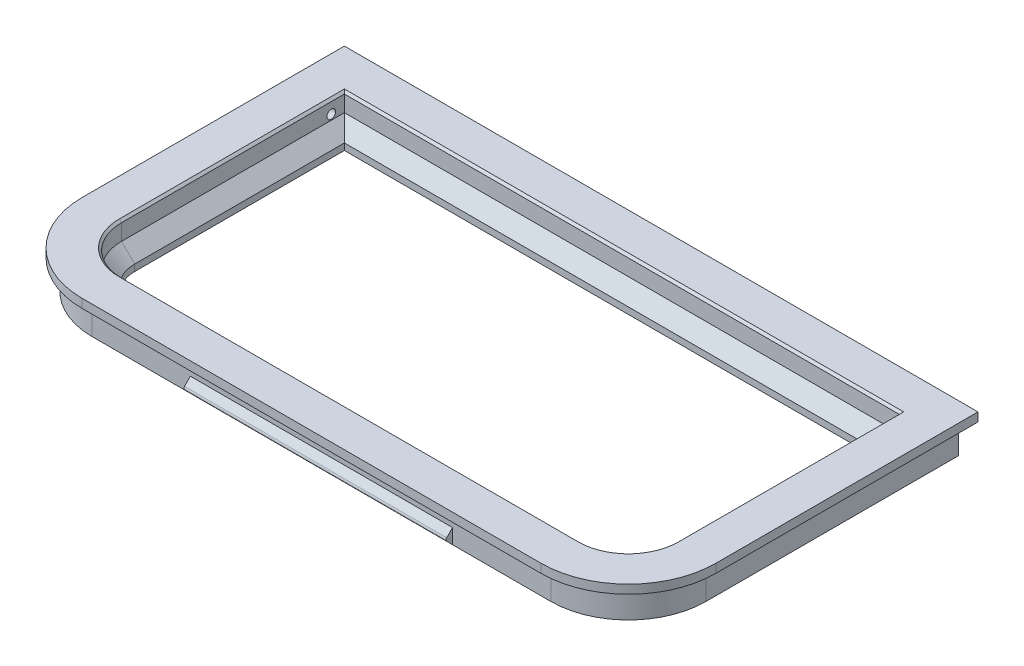
SolidWorks part; units mm, degrees
material "ПК/АБС"
ref_plane "Спереди" through (0, 0, 0) normal (0, 0, 1) x (1, 0, 0)
ref_plane "Сверху" through (0, 0, 0) normal (0, 1, 0) x (1, 0, 0)
ref_plane "Справа" through (0, 0, 0) normal (1, 0, 0) x (0, 0, -1)
sketch "Эскиз1" plane through (0, 0, 0) normal (0, 1, 0) x (1, 0, 0)
  line L1 (-72.5, -40) -> (72.5, -40)
  line L2 (-72.5, -40) -> (-72.5, 40)
  line L3 (-72.5, 40) -> (72.5, 40)
  line L4 (72.5, -40) -> (72.5, 40)
  line L5 (-72.5, -40) -> (72.5, 40) construction
  line L6 (-72.5, 40) -> (72.5, -40) construction
  point P0 (0, 0)
  dimension "D1" = 145
  dimension "D2" = 80
extrude "Бобышка-Вытянуть1" add sketch "Эскиз1" along normal blind 2
fillet "Скругление1" radius 20 2 edges at (-72.5, 1, 40) (72.5, 1, 40)
sketch "Эскиз2" plane through (0, 2, 0) normal (0, 1, 0) x (1, 0, 0)
  line L8 (-63.5, 31) -> (-63.5, -20)
  line L9 (-52.5, -31) -> (52.5, -31)
  line L10 (63.5, -20) -> (63.5, 31)
  line L11 (63.5, 31) -> (-63.5, 31)
  line L12 (-63.5, 31) -> (-63.5, -20)
  line L13 (-52.5, -31) -> (52.5, -31)
  line L14 (63.5, -20) -> (63.5, 31)
  line L15 (63.5, 31) -> (-63.5, 31)
  arc A4 (-63.5, -20) -> (-52.5, -31) centre (-52.5, -20) ccw
  arc A5 (52.5, -31) -> (63.5, -20) centre (52.5, -20) ccw
  arc A6 (-63.5, -20) -> (-52.5, -31) centre (-52.5, -20) ccw
  arc A7 (52.5, -31) -> (63.5, -20) centre (52.5, -20) ccw
  dimension "D1" = 9
extrude "Вырез-Вытянуть1" cut sketch "Эскиз2" against normal blind 2
sketch "Эскиз3" plane through (0, 0, 0) normal (0, -1, 0) x (1, 0, 0)
  line L15 (-63.5, -31) -> (-63.5, 20) construction
  line L16 (63.5, -31) -> (-63.5, -31) construction
  line L17 (63.5, 20) -> (63.5, -31) construction
  line L18 (-52.5, 31) -> (52.5, 31) construction
  line L19 (70.25, -37.75) -> (70.25, 20)
  line L20 (-70.25, -37.75) -> (70.25, -37.75)
  line L21 (-70.25, 20) -> (-70.25, -37.75)
  line L22 (52.5, 37.75) -> (-52.5, 37.75)
  line L23 (70.25, -37.75) -> (70.25, 20)
  line L24 (-70.25, -37.75) -> (70.25, -37.75)
  line L25 (-70.25, 20) -> (-70.25, -37.75)
  line L26 (52.5, 37.75) -> (-52.5, 37.75)
  line L27 (-63.5, -31) -> (-63.5, 20)
  line L28 (63.5, -31) -> (-63.5, -31)
  line L29 (63.5, 20) -> (63.5, -31)
  line L30 (-52.5, 31) -> (52.5, 31)
  arc A6 (-52.5, 31) -> (-63.5, 20) centre (-52.5, 20) ccw construction
  arc A7 (63.5, 20) -> (52.5, 31) centre (52.5, 20) ccw construction
  arc A8 (70.25, 20) -> (52.5, 37.75) centre (52.5, 20) ccw
  arc A9 (-52.5, 37.75) -> (-70.25, 20) centre (-52.5, 20) ccw
  arc A10 (70.25, 20) -> (52.5, 37.75) centre (52.5, 20) ccw
  arc A11 (-52.5, 37.75) -> (-70.25, 20) centre (-52.5, 20) ccw
  arc A12 (-52.5, 31) -> (-63.5, 20) centre (-52.5, 20) ccw
  arc A13 (63.5, 20) -> (52.5, 31) centre (52.5, 20) ccw
  dimension "D1" = 6.75
extrude "Бобышка-Вытянуть2" add sketch "Эскиз3" along normal blind 2
sketch "Эскиз5" plane through (0, 0, 0) normal (1, 0, 0) x (0, 0, -1)
  line L0 (-20, 0) -> (40, 0) construction
  line L7 (37.75, -2) -> (31, -2)
  line L9 (31, -2) -> (31, -6.7)
  line L10 (31, -6.7) -> (37.75, -6.7)
  line L11 (37.75, -6.7) -> (39.45, -5)
  line L12 (39.45, -5) -> (37.75, -3.3)
  line L13 (37.75, -3.3) -> (37.75, -2)
  line L14 (31, -2) -> (31, 2) construction
  line L15 (31, -2) -> (31, 2) construction
  line L16 (-31, -2) -> (-31, 2) construction
  line L17 (-31, -2) -> (-31, 2) construction
  line L18 (-31, -2) -> (-31, -6.7)
  line L19 (-31, -6.7) -> (-37.75, -6.7)
  line L20 (-37.75, -6.7) -> (-39.45, -5)
  line L21 (-39.45, -5) -> (-37.75, -3.3)
  line L22 (-37.75, -3.3) -> (-37.75, -2)
  line L23 (-37.75, -2) -> (-31, -2)
  dimension "D1" = 5
  dimension "D2" = 1.7
  dimension "D4" = 1.7
extrude "Бобышка-Вытянуть4" add sketch "Эскиз5" along normal mid plane 15
sketch "Эскиз6" plane through (0, 0, 0) normal (1, 0, 0) x (0, 0, -1)
  line L6 (-39.45, -5) -> (-37.75, -6.7)
  line L7 (-37.75, -6.7) -> (-31, -6.7)
  line L8 (-31, -6.7) -> (-31, -2)
  line L9 (-31, -2) -> (-37.75, -2)
  line L10 (-37.75, -2) -> (-37.75, -3.3)
  line L11 (-37.75, -3.3) -> (-39.45, -5)
  line L12 (-39.45, -5) -> (-37.75, -6.7)
  line L13 (-37.75, -6.7) -> (-31, -6.7)
  line L14 (-31, -6.7) -> (-31, -2)
  line L15 (-31, -2) -> (-37.75, -2)
  line L16 (-37.75, -2) -> (-37.75, -3.3)
  line L17 (-37.75, -3.3) -> (-39.45, -5)
  dimension "D1" = 0
extrude "Бобышка-Вытянуть5" add sketch "Эскиз6" along normal mid plane 60
fillet "Скругление2" radius 0.5 2 edges at (0, -5, 39.45) (0, -5, -39.45)
sketch "Эскиз7" plane through (0, -2, 0) normal (0, -1, 0) x (1, 0, 0)
  line L7 (-30, 31) -> (-30, 37.75)
  line L8 (-52.5, 31) -> (-30, 31)
  line L10 (30, 37.75) -> (30, 31)
  line L11 (-70.25, 20) -> (-70.25, -37.75)
  line L12 (-70.25, -37.75) -> (-7.5, -37.75)
  line L13 (-7.5, -37.75) -> (-7.5, -31)
  line L14 (-7.5, -31) -> (-63.5, -31)
  line L15 (-63.5, -31) -> (-63.5, 20)
  line L16 (-52.5, 31) -> (-30, 31)
  line L19 (-70.25, 20) -> (-70.25, -37.75)
  line L20 (-70.25, -37.75) -> (-7.5, -37.75)
  line L21 (-7.5, -37.75) -> (-7.5, -31)
  line L22 (-7.5, -31) -> (-63.5, -31)
  line L23 (-63.5, -31) -> (-63.5, 20)
  line L25 (30, 31) -> (52.5, 31)
  line L26 (63.5, 20) -> (63.5, -31)
  line L27 (63.5, -31) -> (7.5, -31)
  line L28 (7.5, -31) -> (7.5, -37.75)
  line L29 (7.5, -37.75) -> (70.25, -37.75)
  line L30 (70.25, -37.75) -> (70.25, 20)
  line L33 (30, 31) -> (52.5, 31)
  line L34 (63.5, 20) -> (63.5, -31)
  line L35 (63.5, -31) -> (7.5, -31)
  line L36 (7.5, -31) -> (7.5, -37.75)
  line L37 (7.5, -37.75) -> (70.25, -37.75)
  line L38 (70.25, -37.75) -> (70.25, 20)
  line L40 (-30, 31) -> (-30, 37.75)
  line L41 (-30, 37.75) -> (-52.5, 37.75)
  line L42 (-30, 37.75) -> (-52.5, 37.75)
  line L43 (30, 37.75) -> (30, 31)
  line L44 (52.5, 37.75) -> (30, 37.75)
  line L45 (52.5, 37.75) -> (30, 37.75)
  arc A2 (-52.5, 37.75) -> (-70.25, 20) centre (-52.5, 20) ccw
  arc A3 (-52.5, 31) -> (-63.5, 20) centre (-52.5, 20) ccw
  arc A4 (-52.5, 37.75) -> (-70.25, 20) centre (-52.5, 20) ccw
  arc A5 (-52.5, 31) -> (-63.5, 20) centre (-52.5, 20) ccw
  arc A6 (63.5, 20) -> (52.5, 31) centre (52.5, 20) ccw
  arc A7 (70.25, 20) -> (52.5, 37.75) centre (52.5, 20) ccw
  arc A8 (63.5, 20) -> (52.5, 31) centre (52.5, 20) ccw
  arc A9 (70.25, 20) -> (52.5, 37.75) centre (52.5, 20) ccw
  dimension "D1" = 0
  dimension "D2" = 0
extrude "Бобышка-Вытянуть6" add sketch "Эскиз7" along normal up to surface (4.7 mm away) up to face at (0, -6.7, 34.375)
sketch "Эскиз10" plane through (0, -6.7, 0) normal (0, -1, 0) x (1, 0, 0)
  line L14 (-63.5, 20) -> (-63.5, -31) construction
  line L15 (63.5, -31) -> (-63.5, -31) construction
  line L16 (63.5, -31) -> (63.5, 20) construction
  line L17 (52.5, 31) -> (-52.5, 31) construction
  line L18 (60.5, -28) -> (60.5, 20)
  line L19 (-60.5, -28) -> (60.5, -28)
  line L20 (-60.5, 20) -> (-60.5, -28)
  line L21 (52.5, 28) -> (-52.5, 28)
  line L22 (60.5, -28) -> (60.5, 20)
  line L23 (-60.5, -28) -> (60.5, -28)
  line L24 (-60.5, 20) -> (-60.5, -28)
  line L25 (52.5, 28) -> (-52.5, 28)
  line L26 (-63.5, 20) -> (-63.5, -31)
  line L27 (63.5, -31) -> (-63.5, -31)
  line L28 (63.5, -31) -> (63.5, 20)
  line L29 (52.5, 31) -> (-52.5, 31)
  arc A7 (-52.5, 31) -> (-63.5, 20) centre (-52.5, 20) ccw construction
  arc A8 (63.5, 20) -> (52.5, 31) centre (52.5, 20) ccw construction
  arc A9 (60.5, 20) -> (52.5, 28) centre (52.5, 20) ccw
  arc A10 (-52.5, 28) -> (-60.5, 20) centre (-52.5, 20) ccw
  arc A11 (60.5, 20) -> (52.5, 28) centre (52.5, 20) ccw
  arc A12 (-52.5, 28) -> (-60.5, 20) centre (-52.5, 20) ccw
  arc A13 (-52.5, 31) -> (-63.5, 20) centre (-52.5, 20) ccw
  arc A14 (63.5, 20) -> (52.5, 31) centre (52.5, 20) ccw
  dimension "D1" = 3
extrude "Бобышка-Вытянуть9" add sketch "Эскиз10" against normal blind 1.5
chamfer "Фаска2" distance 3 angle 45 6 edges at (0, -5.2, -31) (63.5, -5.2, -5.5) (-63.5, -5.2, -5.5) (60.2782, -5.2, 27.7782) (-60.2782, -5.2, 27.7782) (0, -5.2, 31)
sketch "Эскиз11" plane through (70.25, 0, 0) normal (1, 0, 0) x (0, 0, -1)
  line L0 (40, 2) -> (40, 0) construction
  line L1 (-20, 2) -> (40, 2) construction
  circle A0 centre (28, -1) radius 1
  dimension "D1" = 2
  dimension "D2" = 12
  dimension "D3" = 3
extrude "Вырез-Вытянуть2" cut sketch "Эскиз11" against normal through all
chamfer "Фаска3" distance 0.5 angle 45 6 edges at (63.5, 2, -5.5) (60.2782, 2, 27.7782) (0, 2, 31) (-60.2782, 2, 27.7782) (-63.5, 2, -5.5) (0, 2, -31)
sketch "Эскиз12" plane through (0, 0, 0) normal (1, 0, 0) x (0, 0, -1)
  line L3 (39.0964, -4.6464) -> (37.75, -3.3)
  line L4 (37.75, -3.3) -> (37.75, -6.7)
  line L5 (37.75, -6.7) -> (39.0964, -5.3536)
  line L6 (39.0964, -4.6464) -> (37.75, -3.3)
  line L7 (37.75, -3.3) -> (37.75, -6.7)
  line L8 (37.75, -6.7) -> (39.0964, -5.3536)
  arc A1 (39.0964, -5.3536) -> (39.0964, -4.6464) centre (38.7429, -5) ccw
  arc A2 (39.0964, -5.3536) -> (39.0964, -4.6464) centre (38.7429, -5) ccw
  dimension "D1" = 0
extrude "Бобышка-Вытянуть10" add sketch "Эскиз12" along normal mid plane 120
